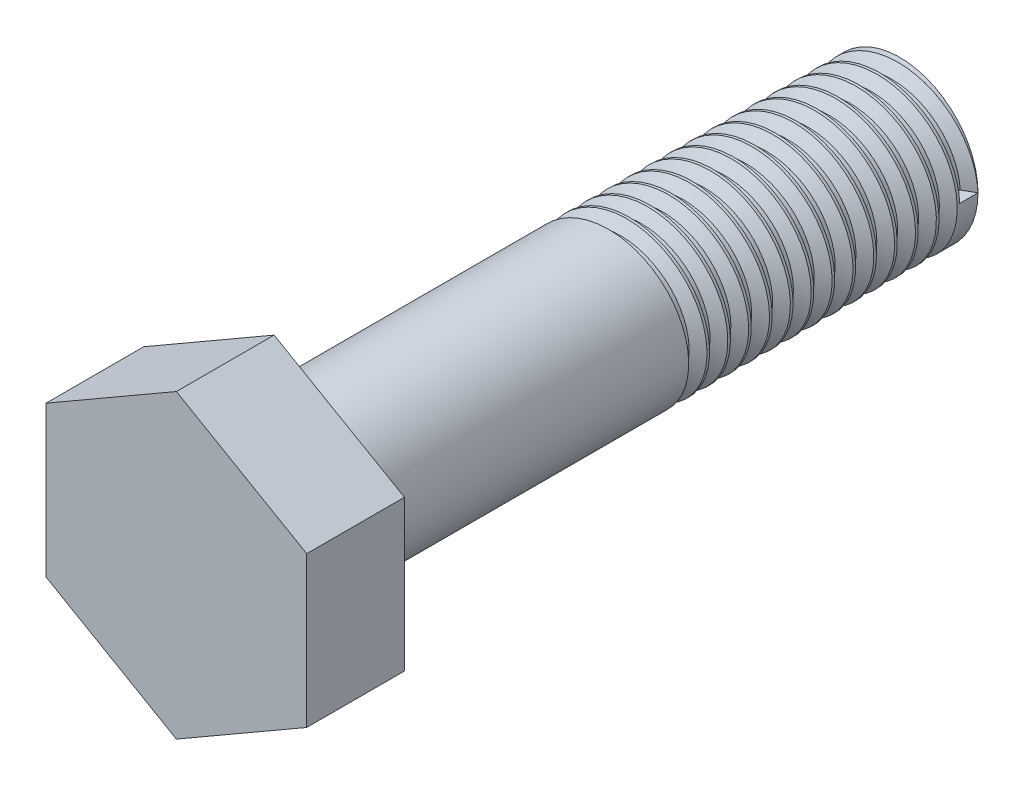
SolidWorks part; units mm, degrees
ref_plane "Front Plane" through (0, 0, 0) normal (0, 0, 1) x (1, 0, 0)
ref_plane "Top Plane" through (0, 0, 0) normal (0, 1, 0) x (1, 0, 0)
ref_plane "Right Plane" through (0, 0, 0) normal (1, 0, 0) x (0, 0, -1)
sketch "Sketch1" plane through (0, 0, 0) normal (0, 0, 1) x (1, 0, 0)
  circle A0 centre (0, 0) radius 9.525
  dimension "D1" = 19.05
extrude "Boss-Extrude1" add sketch "Sketch1" along normal mid plane 76.2
sketch "Sketch2" plane through (0, 0, 38.1) normal (0, 0, 1) x (1, 0, 0)
  line L0 (-19.9504, 0) -> (19.9504, 0) construction
  line L1 (0, -14.1595) -> (0, 14.1595) construction
  line L3 (0, 18.3309) -> (-15.875, 9.1654)
  line L4 (-15.875, 9.1654) -> (-15.875, -9.1654)
  line L5 (-15.875, -9.1654) -> (0, -18.3309)
  line L6 (0, -18.3309) -> (15.875, -9.1654)
  line L7 (15.875, -9.1654) -> (15.875, 9.1654)
  line L8 (15.875, 9.1654) -> (0, 18.3309)
  circle A0 centre (0, 0) radius 15.875 construction
  point P5 (0, 0)
  point P9 (0, 0)
  dimension "D1" = 31.75
extrude "Boss-Extrude2" add sketch "Sketch2" along normal blind 11.9062
thread "Thread1" pitch 2.54 method cut profile "Thread Profile1" start angle 0, offset 0, length 34.29, pitch 2.54, diameter 19.05
ref_plane "Plane1" through (9.525, 0, -38.1) normal (0, -1, 0) x (1, 0, 0)
sketch "Thread Profile1" plane through (9.525, 0, -38.1) normal (0, -1, 0) x (1, 0, 0)
  line L0 (0, 0) -> (0, 2.54) construction
  line L11 (0, 0) -> (0, 2.2225)
  line L12 (0, 2.2225) -> (-1.3748, 1.4287)
  line L13 (-1.3748, 1.4287) -> (-1.3748, 0.7937)
  line L15 (-1.3748, 0.7937) -> (0, 0)
  line L17 (-1.3748, 1.1112) -> (0, 1.1112) construction
  point P2 (0, 0)
  dimension "Pitch" = 2.54
  dimension "Profile_Angle" = 60
  dimension "Profile_Land" = 0.635
  dimension "Profile_Height" = 1.3748
